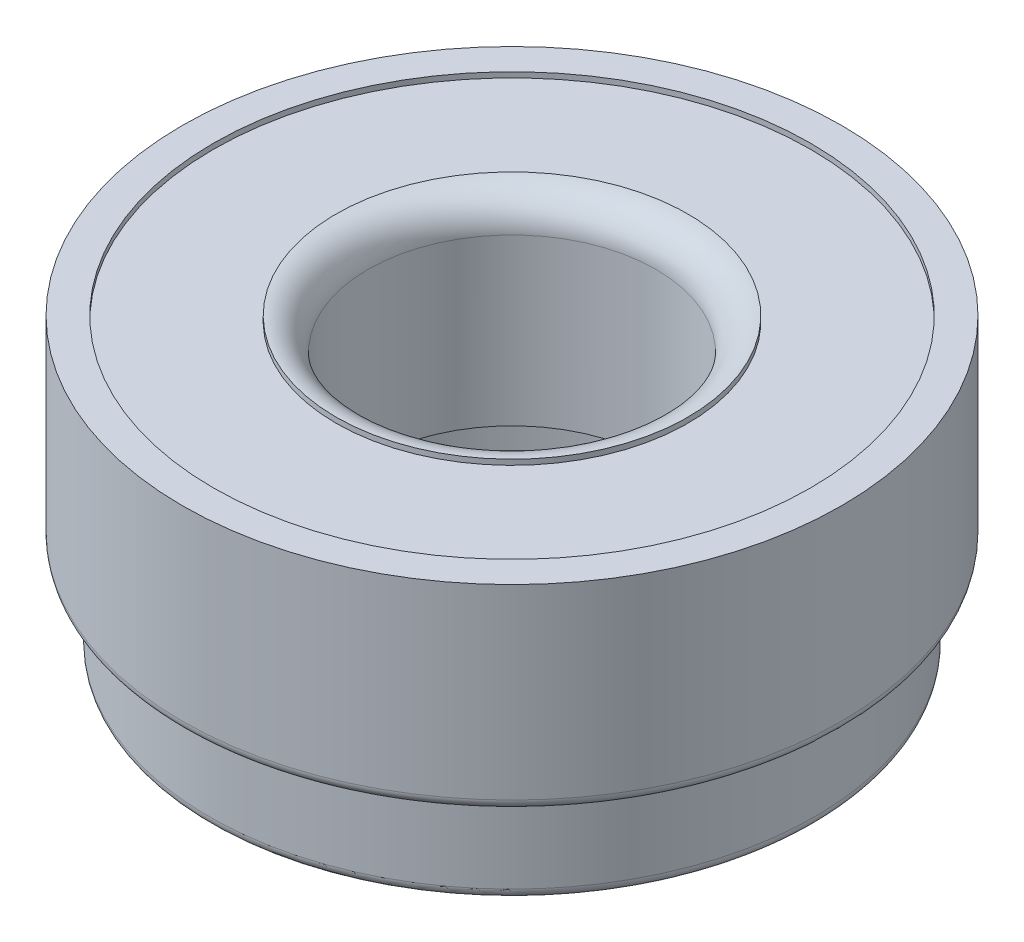
SolidWorks part; units mm, degrees
ref_plane "Спереди" through (0, 0, 0) normal (0, 0, 1) x (1, 0, 0)
ref_plane "Сверху" through (0, 0, 0) normal (0, 1, 0) x (1, 0, 0)
ref_plane "Справа" through (0, 0, 0) normal (1, 0, 0) x (0, 0, -1)
sketch "Эскиз3" plane through (0, 0, 0) normal (0, 0, 1) x (1, 0, 0)
  line L0 (23.4, 0) -> (28.4, 0)
  line L1 (28.4, 0) -> (28.4, 9)
  line L2 (28.4, 9) -> (30.9, 9)
  line L3 (30.9, 9) -> (30.9, 27.5)
  line L4 (30.9, 27.5) -> (13.5, 27.5)
  line L5 (13.5, 27.5) -> (13.5, 9)
  line L6 (13.5, 9) -> (23.4, 9)
  line L7 (23.4, 9) -> (23.4, 0)
  line L8 (0, 0) -> (0, 27.5) construction
  dimension "D1" = 27.5
  dimension "D2" = 13.5
  dimension "D3" = 30.9
  dimension "D4" = 5
  dimension "D5" = 2.5
  dimension "D6" = 9
revolve "Повернуть2" add sketch "Эскиз3" angle 360 about L8
fillet "Скругление1" radius 1 2 edges at (0, 0, -28.4) (0, 9, -30.9)
sketch "Эскиз4" plane through (0, 27.5, 0) normal (0, 1, 0) x (1, 0, 0)
  circle A0 centre (0, 0) radius 28
  circle A1 centre (0, 0) radius 16.5
  dimension "D1" = 33
  dimension "D2" = 56
extrude "Вырез-Вытянуть1" cut sketch "Эскиз4" against normal blind 0.5
fillet "Скругление2" radius 3 1 edges at (0, 27.5, -13.5)
